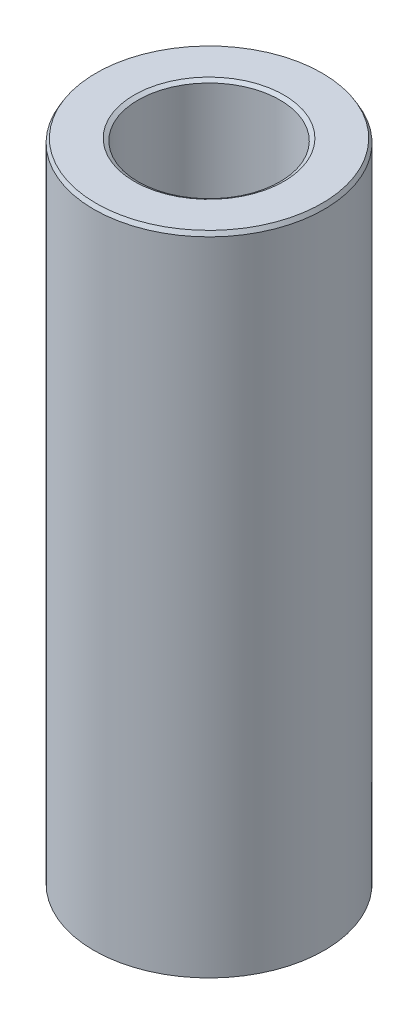
SolidWorks part; units mm, degrees
ref_plane "Front Plane" through (0, 0, 0) normal (0, 0, 1) x (1, 0, 0)
ref_plane "Top Plane" through (0, 0, 0) normal (0, 1, 0) x (1, 0, 0)
ref_plane "Right Plane" through (0, 0, 0) normal (1, 0, 0) x (0, 0, -1)
sketch "Sketch1" plane through (0, 0, 0) normal (0, 1, 0) x (1, 0, 0)
  circle A0 centre (0, 0) radius 47.5
  dimension "SLEEVE_OD" = 95
extrude "Boss-Extrude1" add sketch "Sketch1" along normal blind 267.1245
sketch "Sketch2" plane through (0, 0, 0) normal (0, 1, 0) x (1, 0, 0)
  circle A0 centre (0, 0) radius 29.2197
  dimension "BORE_D" = 58.4393
extrude "Cut-Extrude1" cut sketch "Sketch2" along normal through all
chamfer "Chamfer1" distance 1.6484 angle 30 4 edges at (0, 267.1245, 29.2197) (0, 0, 29.2197) (0, 0, 47.5) (0, 267.1245, 47.5) first distance on face at (0, 267.1245, 29.2197) first distance on face at (0, 0, 29.2197) first distance on face at (0, 267.1245, 47.5)
